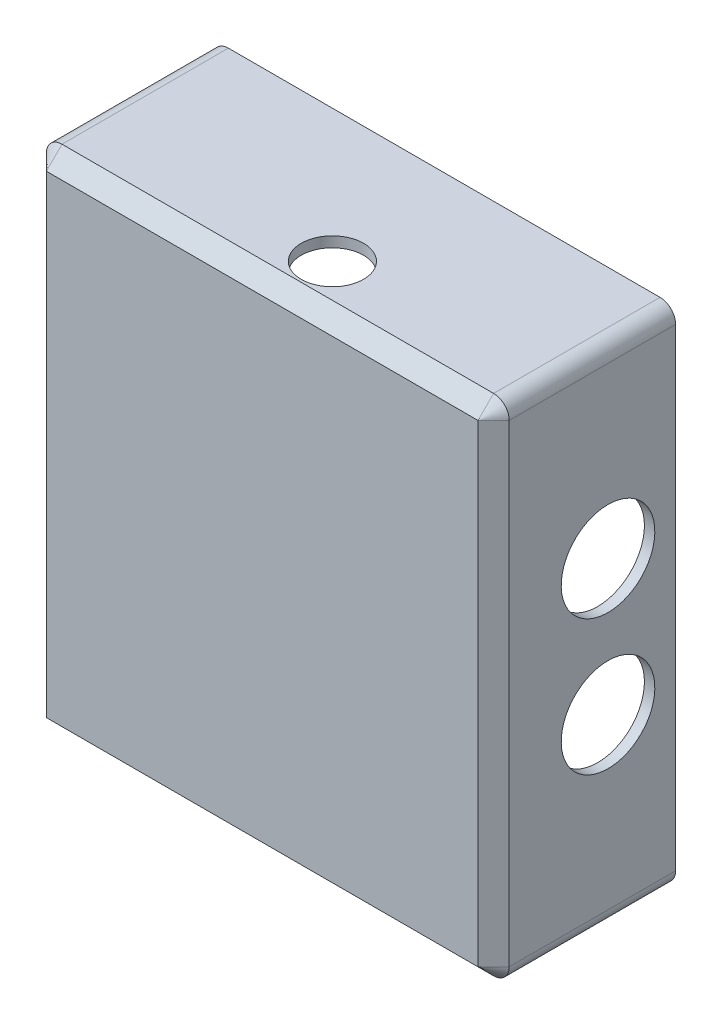
SolidWorks part; units mm, degrees
ref_plane "Front Plane" through (0, 0, 0) normal (0, 0, 1) x (1, 0, 0)
ref_plane "Top Plane" through (0, 0, 0) normal (0, 1, 0) x (1, 0, 0)
ref_plane "Right Plane" through (0, 0, 0) normal (1, 0, 0) x (0, 0, -1)
sketch "Sketch1" plane through (0, 0, 0) normal (0, 0, 1) x (1, 0, 0)
  line L1 (-44.5, 48.5) -> (44.5, 48.5)
  line L2 (-44.5, 48.5) -> (-44.5, -48.5)
  line L3 (-44.5, -48.5) -> (44.5, -48.5)
  line L4 (44.5, 48.5) -> (44.5, -48.5)
  line L5 (-44.5, 48.5) -> (44.5, -48.5) construction
  line L6 (-44.5, -48.5) -> (44.5, 48.5) construction
  point P0 (0, 0)
  dimension "D1" = 89
  dimension "D2" = 97
extrude "Boss-Extrude1" add sketch "Sketch1" along normal blind 35
fillet "Fillet1" radius 3 4 edges at (44.5, 48.5, 17.5) (44.5, -48.5, 17.5) (-44.5, -48.5, 17.5) (-44.5, 48.5, 17.5)
chamfer "Chamfer1" distance 3 angle 45 8 edges at (43.6213, -47.6213, 35) (0, -48.5, 35) (-43.6213, -47.6213, 35) (-44.5, 0, 35) (-43.6213, 47.6213, 35) (0, 48.5, 35) (43.6213, 47.6213, 35) (44.5, 0, 35)
shell "Shell1" thickness 2 removed face at (0, 0, 0)
sketch "Sketch6" plane through (0, 48.5, 0) normal (0, 1, 0) x (1, 0, 0)
  line L0 (41.5, -35) -> (-41.5, -35) construction
  line L2 (44.5, 0) -> (44.5, -32) construction
  circle A0 centre (4, -25.5) radius 6
  point P4 (0, 0)
  dimension "D1" = 9.5
  dimension "D2" = 12
  dimension "D3" = 40.5
extrude "Cut-Extrude5" cut sketch "Sketch6" against normal blind 3
sketch "Sketch7" plane through (44.5, 0, 0) normal (1, 0, 0) x (0, 0, -1)
  line L0 (0, -45.5) -> (0, 45.5) construction
  line L2 (-32, -45.5) -> (0, -45.5) construction
  circle A0 centre (-13, 13) radius 9
  circle A1 centre (-13, -13) radius 9
  point P4 (0, 0)
  point P5 (0, 0)
  point P10 (-13.0157, -43.5)
  dimension "D1" = 18
  dimension "D2" = 26
  dimension "D3" = 13
  dimension "D4" = 32.5
extrude "Cut-Extrude6" cut sketch "Sketch7" against normal blind 10
sketch "Sketch10" plane through (-42.5, 0, 0) normal (1, 0, 0) x (0, 0, -1)
  circle A0 centre (-13, 13) radius 9
  circle A1 centre (-13, -13) radius 9
extrude "Cut-Extrude7" cut sketch "Sketch10" against normal blind 10
sketch "Sketch12" plane through (0, -48.5, 0) normal (0, -1, 0) x (1, 0, 0)
  line L0 (-41.5, 0) -> (41.5, 0) construction
  line L1 (-41.5, 32) -> (-41.5, 0) construction
  circle A0 centre (-13, 13) radius 9
  circle A1 centre (13, 13) radius 9
  point P4 (0, 0)
  dimension "D1" = 18
  dimension "D2" = 26
  dimension "D3" = 13
  dimension "D4" = 28.5
extrude "Cut-Extrude8" cut sketch "Sketch12" against normal blind 10
